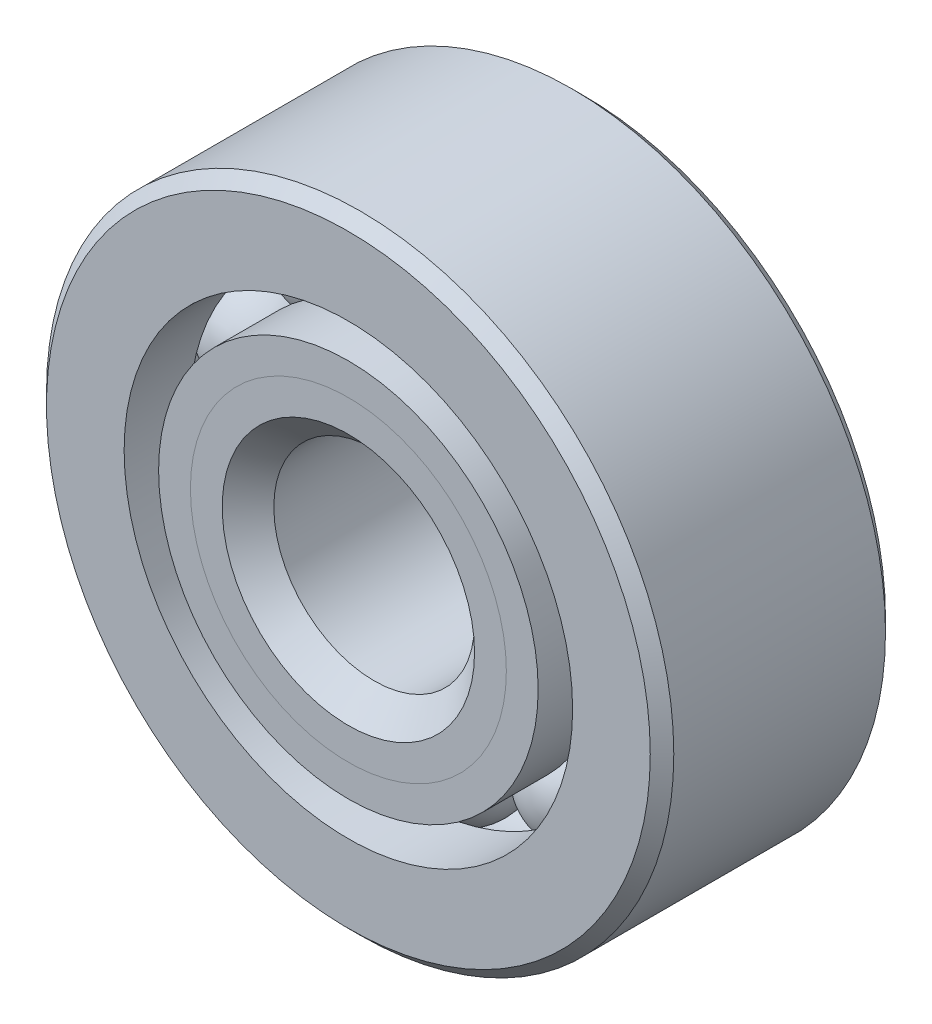
SolidWorks part; units mm, degrees
ref_plane "Front Plane" through (0, 0, 0) normal (0, 0, 1) x (1, 0, 0)
ref_plane "Top Plane" through (0, 0, 0) normal (0, 1, 0) x (1, 0, 0)
ref_plane "Right Plane" through (0, 0, 0) normal (1, 0, 0) x (0, 0, -1)
sketch "Sketch1" plane through (0, 0, 0) normal (1, 0, 0) x (0, 0, -1)
  line L0 (-0.5953, 0) -> (0.5953, 0) construction
  line L1 (0, 1.5875) -> (0, -1.5875) construction
  line L2 (0.5358, 1.5875) -> (-0.5358, 1.5875)
  line L3 (-0.5358, 1.5875) -> (-0.5953, 1.528)
  line L4 (-0.5953, 1.528) -> (-0.5953, 1.135)
  line L5 (-0.5953, 1.135) -> (-0.2646, 1.135)
  line L6 (0.5953, 1.135) -> (0.2646, 1.135)
  line L7 (0.5953, 1.528) -> (0.5953, 1.135)
  line L8 (0.5358, 1.5875) -> (0.5953, 1.528)
  line L9 (0, 1.5875) -> (0, 1.0478) construction
  line L10 (0, 1.0478) -> (0, 0.508) construction
  arc A0 (-0.2646, 1.135) -> (0.2646, 1.135) centre (0, 1.0478) cw
  point P14 (0, 0.508)
  dimension "Width" = 1.1906
  dimension "OD" = 3.175
  dimension "D1" = 45
  dimension "D3" = 0.5292
  dimension "D4" = 0.0872
revolve "Revolve1" add sketch "Sketch1" angle 360 about L0
sketch "Sketch2" plane through (0, 0, 0) normal (1, 0, 0) x (0, 0, -1)
  line L0 (-0.5953, 0.9605) -> (-0.2646, 0.9605)
  line L1 (-0.5953, 1.528) -> (-0.5953, -1.528) construction
  line L2 (-0.5953, 0.9605) -> (-0.5953, 0.7996)
  line L3 (-0.5953, 0.7996) -> (-0.4343, 0.6386)
  line L4 (-0.4343, 0.6386) -> (0, 0.6386)
  line L5 (0, 1.5875) -> (0, -1.5875) construction
  line L6 (0, 0.6386) -> (0, 0.7692)
  line L7 (0, 0.7692) -> (0, 0.508) construction
  line L8 (-0.5953, 0.9605) -> (-0.5953, 0.6386) construction
  line L9 (-0.5953, 0.6386) -> (-0.4343, 0.6386) construction
  arc A0 (-0.2646, 0.9605) -> (0, 0.7692) centre (0, 1.0478) ccw
  arc A1 (0.2646, 1.135) -> (-0.2646, 1.135) centre (0, 1.0478) ccw construction
  circle A2 centre (0, 1.0478) radius 0.2786 construction
  dimension "D1" = 45
revolve "Revolve2" add sketch "Sketch2" angle 360 about L0
sketch "Sketch3" plane through (0, 0, 0) normal (1, 0, 0) x (0, 0, -1)
  line L0 (-0.5953, 0.7996) -> (-0.4343, 0.6386)
  line L1 (-0.4343, 0.6386) -> (0, 0.6386)
  line L2 (0, 0.6386) -> (0, 0.7692)
  line L3 (-0.5953, 0.7996) -> (-0.5953, 0.6386)
  line L4 (-0.5953, 0.9605) -> (-0.5953, 0.6386) construction
  line L5 (-0.5953, 0.6386) -> (-0.4647, 0.508)
  line L6 (-0.4647, 0.508) -> (0.5358, 0.508)
  line L7 (0.5358, 1.5875) -> (0.5358, -1.5875) construction
  line L8 (0.5358, 0.508) -> (0.5953, 0.5675)
  line L9 (0.5953, -1.528) -> (0.5953, 1.528) construction
  line L10 (0.5953, 0.5675) -> (0.5953, 0.9605)
  line L11 (0.5953, 0.9605) -> (0.2646, 0.9605)
  line L13 (0.5358, 1.5875) -> (0.5953, 1.528) construction
  circle A0 centre (0, 1.0478) radius 0.2786 construction
  arc A1 (0.2646, 0.9605) -> (0, 0.7692) centre (0, 1.0478) cw
revolve "Revolve3" add sketch "Sketch3" angle 360 about L0
sketch "Sketch4" plane through (0, 0, 0) normal (1, 0, 0) x (0, 0, -1)
  line L0 (-0.2786, 1.0478) -> (0.2786, 1.0478)
  circle A1 centre (0, 1.0478) radius 0.2786 construction
  arc A2 (-0.2786, 1.0478) -> (0.2786, 1.0478) centre (0, 1.0478) cw
  arc A3 (0.2646, 1.135) -> (-0.2646, 1.135) centre (0, 1.0478) ccw construction
revolve "Revolve4" add sketch "Sketch4" angle 360 about L0
ref_axis "Axis1" through (0, 0, -0.5953) along (0, 0, 1)
pattern_circular "CirPattern1" count 10 over 360 about axis through (0, 0, -0.5953) along (0, 0, 1) of bodies 104
equation "\"D2@Sketch1\" = \"Width@Sketch1\"*.05"
equation "\"D3@Sketch1\" = \"Width@Sketch1\"/2.25"
equation "\"D4@Sketch1\" = (((\"OD@Sketch1\"-\"Width@Sketch1\")/2)/3.25)/3.5"
equation "\"D2@CirPattern1\" = 360/\"Balls@CirPattern1\""
